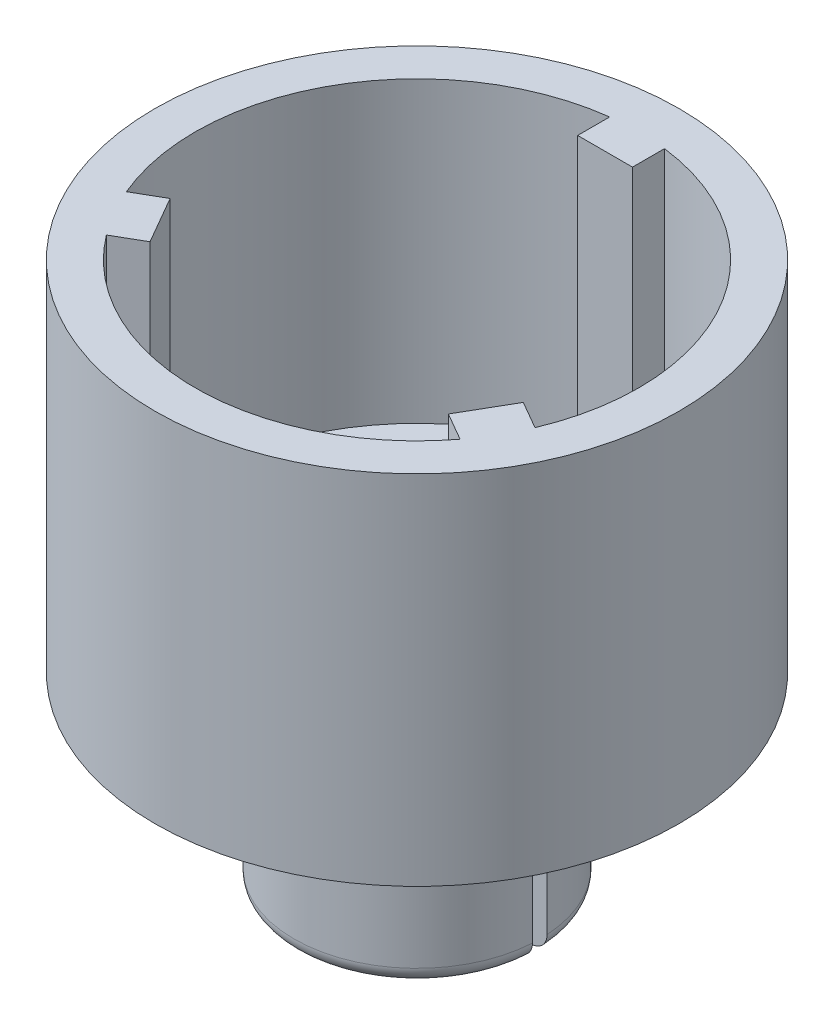
SolidWorks part; units mm, degrees
ref_plane "Front Plane" through (0, 0, 0) normal (0, 0, 1) x (1, 0, 0)
ref_plane "Top Plane" through (0, 0, 0) normal (0, 1, 0) x (1, 0, 0)
ref_plane "Right Plane" through (0, 0, 0) normal (1, 0, 0) x (0, 0, -1)
sketch "Sketch1" plane through (0, 0, 0) normal (0, 1, 0) x (1, 0, 0)
  circle A0 centre (0, 0) radius 32.5
  dimension "D1" = 65
extrude "Boss-Extrude1" add sketch "Sketch1" along normal blind 44.3
sketch "Sketch2" plane through (0, 44.3, 0) normal (0, 1, 0) x (1, 0, 0)
  circle A0 centre (0, 0) radius 27.5
  dimension "D1" = 55
extrude "Cut-Extrude1" cut sketch "Sketch2" against normal blind 37
sketch "Sketch3" plane through (0, 0, 0) normal (0, -1, 0) x (1, 0, 0)
  circle A0 centre (0, 0) radius 19.5
  dimension "D1" = 39
extrude "Boss-Extrude2" add sketch "Sketch3" along normal blind 7
sketch "Sketch4" plane through (0, -7, 0) normal (0, -1, 0) x (1, 0, 0)
  circle A0 centre (0, 0) radius 15.25
  dimension "D1" = 30.5
extrude "Boss-Extrude3" add sketch "Sketch4" along normal blind 16
fillet "Fillet1" radius 5 1 edges at (0, 0, -19.5)
sketch "Sketch7" plane through (0, -23, 0) normal (0, -1, 0) x (1, 0, 0)
  line L1 (33.0968, 0.9034) -> (-33.0968, 0.9034)
  line L2 (33.0968, 0.9034) -> (33.0968, -0.9034)
  line L3 (33.0968, -0.9034) -> (-33.0968, -0.9034)
  line L4 (-33.0968, 0.9034) -> (-33.0968, -0.9034)
  line L5 (33.0968, 0.9034) -> (-33.0968, -0.9034) construction
  line L6 (33.0968, -0.9034) -> (-33.0968, 0.9034) construction
  point P0 (0, 0)
extrude "Cut-Extrude2" cut sketch "Sketch7" against normal up to surface (16 mm away) up to face at (0, -7, -15.25)
fillet "Fillet2" radius 2 2 edges at (0, -23, 15.25) (0, -23, -15.25)
sketch "Sketch9" plane through (0, 7.3, 0) normal (0, 1, 0) x (1, 0, 0)
  circle A0 centre (0, 0) radius 7.5
  dimension "D1" = 15
extrude "Cut-Extrude3" cut sketch "Sketch9" against normal through all
sketch "Sketch11" plane through (0, 44.3, 0) normal (0, 1, 0) x (1, 0, 0)
  line L0 (0, 0) -> (0, -50000) construction
  line L6 (3.4, 32.3217) -> (-3.4, 32.3217)
  line L7 (3.4, 32.3217) -> (3.4, 23.3217)
  line L8 (3.4, 23.3217) -> (-3.4, 23.3217)
  line L9 (-3.4, 32.3217) -> (-3.4, 23.3217)
  circle A2 centre (0, 0) radius 32.5 construction
  point P9 (0, 0)
  point P10 (-4.3205, 32.2115)
  dimension "D1" = 6.8
  dimension "D2" = 9
extrude "Boss-Extrude4" add sketch "Sketch11" against normal up to next
pattern_circular "CirPattern1" count 3 over 360 about axis through (0, 44.3, 0) along (0, 1, 0) of "Boss-Extrude4"
